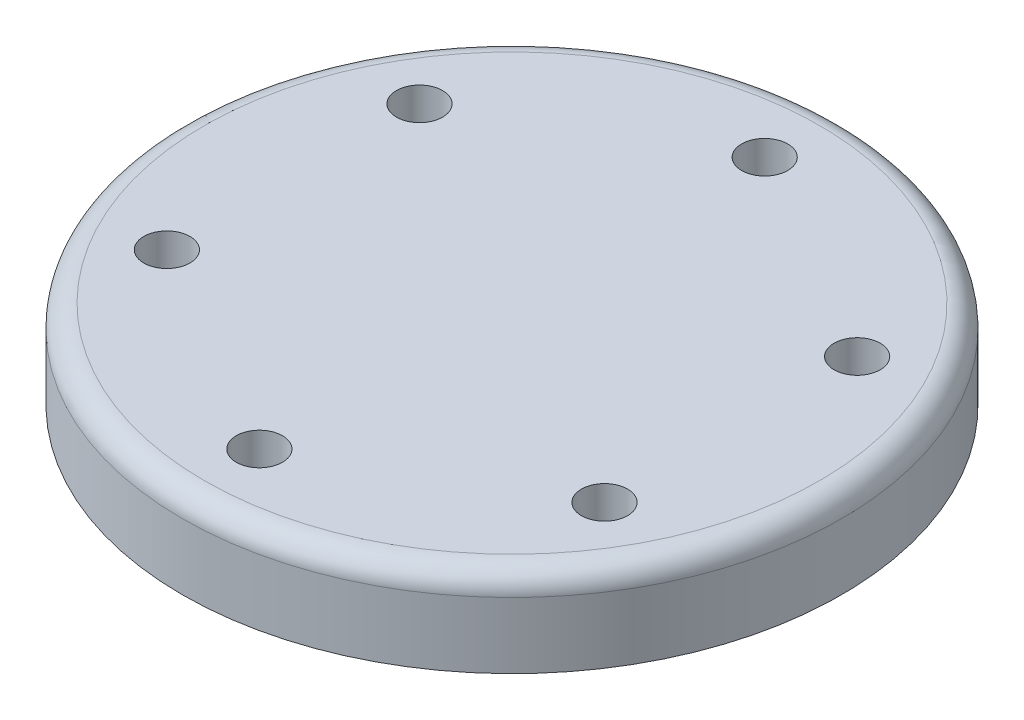
SolidWorks part; units mm, degrees
material "PEI"
ref_plane "Front Plane" through (0, 0, 0) normal (0, 0, 1) x (1, 0, 0)
ref_plane "Top Plane" through (0, 0, 0) normal (0, 1, 0) x (1, 0, 0)
ref_plane "Right Plane" through (0, 0, 0) normal (1, 0, 0) x (0, 0, -1)
sketch "Sketch1" plane through (0, 0, 0) normal (0, 1, 0) x (1, 0, 0)
  circle A0 centre (0, 0) radius 30
  circle A1 centre (0, 0) radius 23 construction
  circle A2 centre (0, 23) radius 2.1
  circle A3 centre (19.9191, 11.5009) radius 2.1
  circle A4 centre (19.9201, -11.4991) radius 2.1
  circle A5 centre (0.002, -23) radius 2.1
  circle A6 centre (-19.9171, -11.5009) radius 2.1
  circle A7 centre (-19.9181, 11.4991) radius 2.1
  point P18 (0.001, 0)
  dimension "D1" = 60
  dimension "D2" = 46
  dimension "D3" = 4.2
  dimension "D4" = 6
extrude "Boss-Extrude1" add sketch "Sketch1" along normal blind 8
fillet "Fillet1" radius 2 1 edges at (0, 8, 30)
